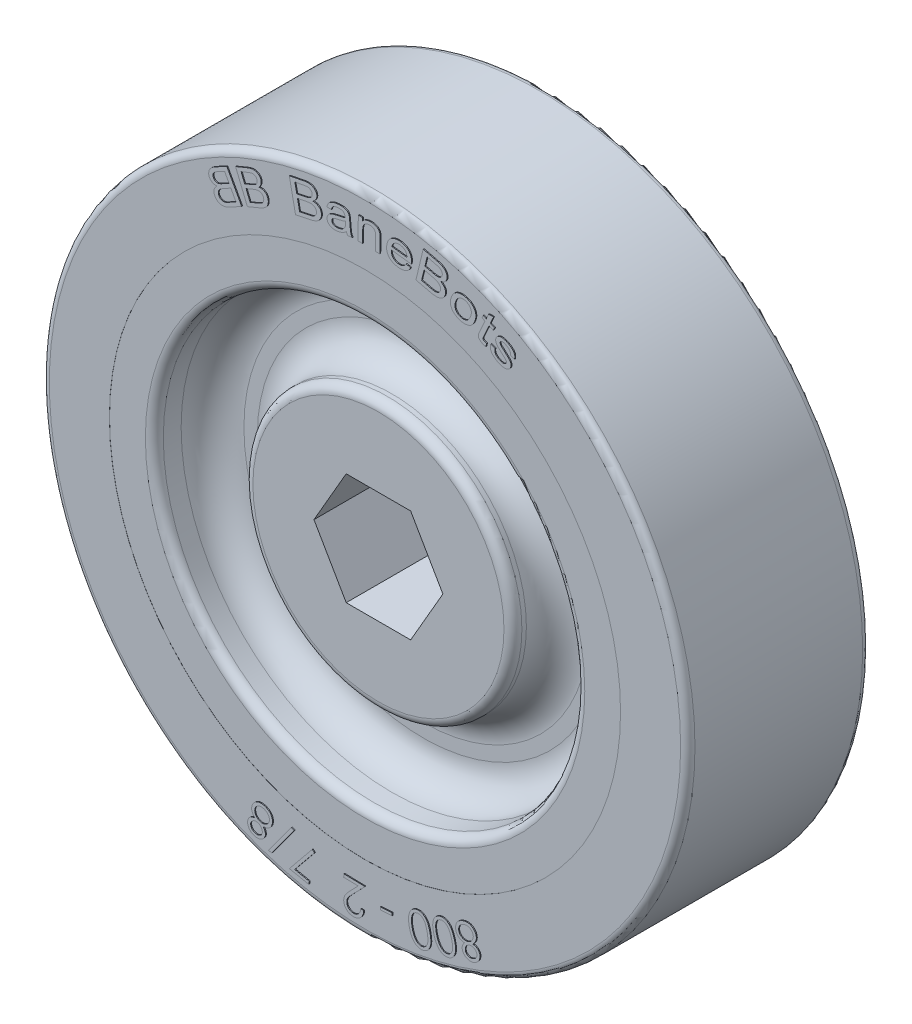
SolidWorks part; units mm, degrees
ref_plane "Front Plane" through (0, 0, 0) normal (0, 0, 1) x (1, 0, 0)
ref_plane "Top Plane" through (0, 0, 0) normal (0, 1, 0) x (1, 0, 0)
ref_plane "Right Plane" through (0, 0, 0) normal (1, 0, 0) x (0, 0, -1)
sketch "Sketch1" plane through (0, 0, 0) normal (0, 0, 1) x (1, 0, 0)
  line L1 (3.594, -6.225) -> (7.188, 0)
  line L2 (7.188, 0) -> (3.594, 6.225)
  line L3 (3.594, 6.225) -> (-3.594, 6.225)
  line L4 (-3.594, 6.225) -> (-7.188, 0)
  line L5 (-7.188, 0) -> (-3.594, -6.225)
  line L6 (-3.594, -6.225) -> (3.594, -6.225)
  circle A0 centre (0, 0) radius 6.225 construction
  circle A1 centre (0, 0) radius 36
  dimension "D1" = 12.45
  dimension "D2" = 72
extrude "Extrude1" add sketch "Sketch1" along normal mid plane 20.3
fillet "Fillet1" radius 0.8 2 edges at (36, 0, -10.15) (36, 0, 10.15)
sketch "Sketch2" plane through (0, 0, 0) normal (0, 1, 0) x (1, 0, 0)
  line L0 (0, 10.15) -> (0, 8.65)
  line L1 (0, 8.65) -> (-15, 8.65)
  line L2 (-15, 8.65) -> (-15, 3.65)
  line L3 (-15, 3.65) -> (-23.5, 3.65)
  line L4 (-23.5, 3.65) -> (-23.5, 10.14)
  line L5 (-23.5, 10.14) -> (-28.5, 10.14)
  line L6 (-28.5, 10.14) -> (-28.5, 10.15)
  line L8 (-28.5, 10.15) -> (0, 10.15)
  dimension "D1" = 0.01
  dimension "D2" = 15
  dimension "D3" = 23.5
  dimension "D4" = 6.5
  dimension "D5" = 1.5
  dimension "D6" = 28.5
revolve "Cut-Revolve1" cut sketch "Sketch2" angle 360 about L0
fillet "Fillet2" radius 1 2 edges at (-23.5, 0, -10.14) (-15, 0, -8.65)
fillet "Fillet3" radius 3.5 2 edges at (-15, 0, -3.65) (-23.5, 0, -3.65)
mirror "Mirror1" about plane through (0, 0, 0) normal (0, 0, 1) of "Fillet3", "Fillet2", "Cut-Revolve1"
sketch "Sketch4" plane through (0, 0, -10.15) normal (0, 0, -1) x (-1, 0, 0)
  line L0 (0, 0) -> (-8.33, 29.8599) construction
  line L1 (-13.3409, 27.9825) -> (-15.1484, 31.7737) construction
  line L3 (0, 0) -> (16.4149, 26.2973) construction
  line L4 (0, 0) -> (0, 28.5) construction
  line L5 (0, 0) -> (-16.4149, 26.2973) construction
  line L6 (0, -31) -> (0, 0) construction
  arc A0 (16.4149, 26.2973) -> (-8.33, 29.8599) centre (0, 0) ccw construction
  arc A1 (-10.0963, 29.3098) -> (-16.4149, 26.2973) centre (0, 0) ccw construction
  circle A2 centre (0, 0) radius 35.2 construction
  circle A3 centre (0, 0) radius 28.5 construction
  circle A4 centre (0, 0) radius 28.5 construction
  arc A5 (12.7, -28.2791) -> (-12.7, -28.2791) centre (0, 0) cw construction
  text T0 "BaneBots" font "Arial" height 3.5
  text T1 "800 - 2  7/8"
  dimension "D1" = 62
  dimension "D2" = 25
  dimension "D3" = 7
  dimension "D4" = 1.85
  dimension "D5" = 25.4
extrude "Extrude3" add sketch "Sketch4" along normal blind 0.1
sketch "Sketch5" plane through (0, 0, -10.15) normal (0, 0, -1) x (-1, 0, 0)
  text T0 "B" font "Arial" height 3.5
extrude "Extrude4" add sketch "Sketch5" along normal blind 0.1
ref_plane "Plane1" through (0, 0, 0) normal (0.9027, -0.4304, 0) x (0, 0, -1)
mirror "Mirror2" about plane through (0, 0, 0) normal (0.9027, -0.4304, 0) of "Extrude4"
sketch "Sketch6" plane through (0, 0, 10.15) normal (0, 0, 1) x (1, 0, 0)
  line L0 (0, 0) -> (0, 28.5) construction
  arc A0 (-16.4149, 26.2973) -> (-10.0963, 29.3098) centre (0, 0) cw construction
  arc A1 (8.33, 29.8599) -> (-16.4149, 26.2973) centre (0, 0) ccw construction
  arc A2 (16.4149, 26.2973) -> (-8.33, 29.8599) centre (0, 0) ccw construction
  arc A6 (-12.7, -28.2791) -> (12.7, -28.2791) centre (0, 0) ccw
  arc A7 (-12.7, -28.2791) -> (12.7, -28.2791) centre (0, 0) ccw construction
  text T0 "BaneBots" font "Arial" height 3.5
  text T1 "800 - 2  7/8" font "Century Gothic" height 3.5
  dimension "D1" = 7
  dimension "D3" = 0
  dimension "D2" = 25
extrude "Extrude5" add sketch "Sketch6" along normal blind 0.1
sketch "Sketch7" plane through (0, 0, 10.15) normal (0, 0, 1) x (1, 0, 0)
  line L0 (-13.3409, 27.9825) -> (-15.1484, 31.7737) construction
  arc A2 (-10.0963, 29.3098) -> (-16.4149, 26.2973) centre (0, 0) ccw construction
  circle A3 centre (0, 0) radius 35.2 construction
  text T0 "B" font "Arial" height 3.5
extrude "Extrude6" add sketch "Sketch7" along normal blind 0.1
ref_plane "Plane2" through (0, 0, 0) normal (0.9027, 0.4304, 0) x (0, 0, -1)
mirror "Mirror3" about plane through (0, 0, 0) normal (0.9027, 0.4304, 0) of "Extrude6"
